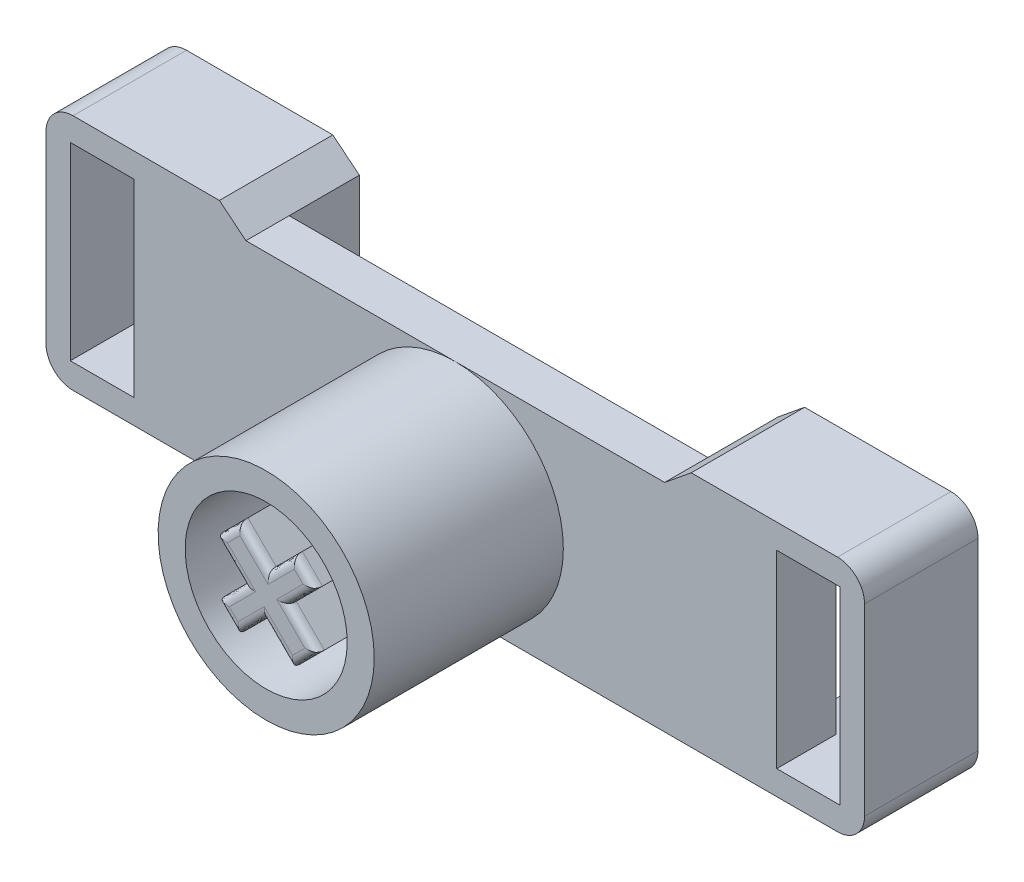
SolidWorks part; units mm, degrees
ref_plane "Front Plane" through (0, 0, 0) normal (0, 0, 1) x (1, 0, 0)
ref_plane "Top Plane" through (0, 0, 0) normal (0, 1, 0) x (1, 0, 0)
ref_plane "Right Plane" through (0, 0, 0) normal (1, 0, 0) x (0, 0, -1)
sketch "Cherry" plane through (0, 0, 0) normal (0, 0, 1) x (1, 0, 0)
  line L0 (-0.8132, -0.0707) -> (-1.8562, 0.9723)
  line L1 (0.9723, -1.8562) -> (-0.0707, -0.8132)
  line L2 (0.9723, -1.8562) -> (1.8562, -0.9723)
  line L3 (1.8562, -0.9723) -> (0.8132, 0.0707)
  line L4 (-1.8562, 0.9723) -> (-0.9723, 1.8562)
  line L6 (0.0707, 0.8132) -> (-0.9723, 1.8562)
  line L7 (-1.043, -1.7854) -> (-1.7854, -1.043)
  line L8 (-1.043, -1.7854) -> (-0.0707, -0.8132)
  line L9 (1.7854, 1.043) -> (1.043, 1.7854)
  line L10 (-1.7854, -1.043) -> (-0.8132, -0.0707)
  line L15 (0.8132, 0.0707) -> (1.7854, 1.043)
  line L18 (0.0707, 0.8132) -> (1.043, 1.7854)
  circle A0 centre (0, 0) radius 3
  circle A1 centre (0, 0) radius 4
extrude "Outer Cylinder" add sketch "Cherry" along normal blind 7 contours L18 L6 L4 L0 L10 L7 L8 L1 L2 L3 L15 L9 | A1 A0 region at (0, 0, 0) region at (-3.8869, 0, 0)
sketch "Inner Gap" plane through (0, 0, 0) normal (0, 0, 1) x (1, 0, 0)
  circle A0 centre (0, 0) radius 3
extrude "Inner Wall" add sketch "Inner Gap" along normal blind 3
fillet "Fillet2" radius 0.3 12 edges at (-1.4142, 1.4142, 7) (-1.3347, 0.4508, 7) (-1.2993, -0.5568, 7) (-1.4142, -1.4142, 7) (-0.5568, -1.2993, 7) (0.4508, -1.3347, 7) (1.4142, -1.4142, 7) (1.3347, -0.4508, 7) (-0.4508, 1.3347, 7) (0.5568, 1.2993, 7) (1.4142, 1.4142, 7) (1.2993, 0.5568, 7) curvature continuous yes
sketch "Sketch2" plane through (0, 0, 0) normal (0, 0, 1) x (1, 0, 0)
  line L0 (-1.8562, 0.9723) -> (-2.8284, 0)
  line L1 (-1.043, -1.7854) -> (-0.0707, -0.8132)
  line L2 (-0.9723, 1.8562) -> (0.0707, 0.8132)
  line L3 (-0.8132, -0.0707) -> (-1.7854, -1.043)
  line L4 (0.9723, -1.8562) -> (0, -2.8284)
  line L5 (0, -1000) -> (0, 49000) construction
  line L6 (-1000, 0) -> (49000, 0) construction
  line L7 (-15.15, -996.1639) -> (-15.15, 49003.8361) construction
  line L8 (-11.7, -997.4571) -> (-11.7, 49002.5429) construction
  line L9 (-14.25, -997.5605) -> (-14.25, 49002.4395) construction
  line L10 (-7.75, -998.1554) -> (-7.75, 49001.8446) construction
  line L11 (-0.9723, 1.8562) -> (0, 2.8284)
  line L12 (-1001.5043, 4) -> (48998.4957, 4) construction
  line L13 (0, 2.8284) -> (1.043, 1.7854)
  line L14 (-1001.5043, -4) -> (48998.4957, -4) construction
  line L15 (0.8132, 0.0707) -> (1.7854, 1.043)
  line L16 (1.7854, 1.043) -> (2.8284, 0)
  line L17 (0.8132, 0.0707) -> (1.8562, -0.9723)
  line L18 (0.0707, 0.8132) -> (1.043, 1.7854)
  line L19 (2.8284, 0) -> (1.8562, -0.9723)
  line L20 (0.9723, -1.8562) -> (-0.0707, -0.8132)
  line L21 (-1004.1116, 4.8) -> (48995.8884, 4.8) construction
  line L22 (-15.15, -3) -> (-15.15, 3.8062)
  line L23 (0, -2.8284) -> (-1.043, -1.7854)
  line L24 (-14.1489, 4.8062) -> (-8.7319, 4.8)
  line L25 (-1.7854, -1.043) -> (-2.8284, 0)
  line L26 (-0.8132, -0.0707) -> (-1.8562, 0.9723)
  line L28 (-7.75, 4) -> (7.75, 4)
  line L29 (-14.15, -4) -> (14.15, -4)
  line L30 (-8.75, -997.4752) -> (-8.75, 49002.5248) construction
  line L31 (-8.7319, 4.8) -> (-7.75, 4)
  line L32 (-1003.474, -3.1) -> (48996.526, -3.1) construction
  line L33 (-1010.3803, 3.9) -> (48989.6197, 3.9) construction
  line L38 (7.75, -998.1554) -> (7.75, 49001.8446) construction
  line L39 (8.75, -997.4752) -> (8.75, 49002.5248) construction
  line L40 (11.7, -997.4571) -> (11.7, 49002.5429) construction
  line L41 (14.25, -997.5605) -> (14.25, 49002.4395) construction
  line L42 (15.15, -996.1639) -> (15.15, 49003.8361) construction
  line L47 (8.7319, 4.8) -> (7.75, 4)
  line L48 (14.1489, 4.8062) -> (8.7319, 4.8)
  line L49 (15.15, -3) -> (15.15, 3.8062)
  arc A0 (15.15, -3) -> (14.15, -4) centre (14.15, -3) cw
  arc A1 (14.1489, 4.8062) -> (15.15, 3.8062) centre (14.15, 3.8062) cw
  arc A2 (-15.15, -3) -> (-14.15, -4) centre (-14.15, -3) ccw
  arc A3 (-15.15, 3.8062) -> (-14.1489, 4.8062) centre (-14.15, 3.8062) cw
  point P41 (0, 4)
  point P69 (0, -4)
  point P71 (15.15, -4)
  point P74 (15.15, 4.8073)
  point P77 (-15.15, -4)
  point P80 (-15.15, 4.8073)
  dimension "D1" = 15.15
  dimension "D10" = 1
  dimension "D2" = 0.9
  dimension "D3" = 2.55
  dimension "D4" = 7.4
  dimension "D5" = 4
  dimension "D6" = 4.8
  dimension "D7" = 1
  dimension "D8" = 0.9
  dimension "D9" = 0.9
extrude "Boss-Extrude1" add sketch "Sketch2" against normal blind 4.2
sketch "Sketch3" plane through (0, 0, 0) normal (0, 0, 1) x (1, 0, 0)
  line L0 (-1.8562, 0.9723) -> (-2.8284, 0)
  line L1 (-1.043, -1.7854) -> (-0.0707, -0.8132)
  line L2 (-0.9723, 1.8562) -> (0.0707, 0.8132)
  line L3 (-0.8132, -0.0707) -> (-1.7854, -1.043)
  line L4 (0.9723, -1.8562) -> (0, -2.8284)
  line L11 (-0.9723, 1.8562) -> (0, 2.8284)
  line L13 (0, 2.8284) -> (1.043, 1.7854)
  line L15 (0.8132, 0.0707) -> (1.7854, 1.043)
  line L16 (1.7854, 1.043) -> (2.8284, 0)
  line L17 (0.8132, 0.0707) -> (1.8562, -0.9723)
  line L18 (0.0707, 0.8132) -> (1.043, 1.7854)
  line L19 (2.8284, 0) -> (1.8562, -0.9723)
  line L20 (0.9723, -1.8562) -> (-0.0707, -0.8132)
  line L23 (0, -2.8284) -> (-1.043, -1.7854)
  line L25 (-1.7854, -1.043) -> (-2.8284, 0)
  line L26 (-0.8132, -0.0707) -> (-1.8562, 0.9723)
extrude "Cut-Extrude1" cut sketch "Sketch3" along normal blind 3 and the other way blind 1.6
sketch "Sketch5" plane through (0, 0, -4.2) normal (0, 0, -1) x (-1, 0, 0)
  line L0 (0, -1000) -> (0, 49000) construction
  line L1 (-7.75, -1000.8733) -> (-7.75, 48999.1267) construction
  line L2 (-1000.8968, 4) -> (48999.1032, 4) construction
  line L3 (-1000, 0) -> (49000, 0) construction
  line L4 (-1000.8968, -4) -> (48999.1032, -4) construction
  line L5 (7.75, -1000.8733) -> (7.75, 48999.1267) construction
  line L7 (-7.75, 4) -> (7.75, 4)
  line L8 (-7.75, 4) -> (-7.75, -4)
  line L9 (-7.75, -4) -> (7.75, -4)
  line L10 (7.75, 4) -> (7.75, -4)
  dimension "D1" = 4
  dimension "D2" = 7.75
extrude "Cut-Extrude2" cut sketch "Sketch5" against normal blind 2.6
sketch "Sketch6" plane through (0, 0, 0) normal (0, 0, 1) x (1, 0, 0)
  line L0 (1010.3803, 3.9) -> (-48989.6197, 3.9) construction
  line L1 (-14.25, 3.9) -> (-11.9, 3.9)
  line L2 (-14.25, 3.9) -> (-14.25, -3.1)
  line L3 (-14.25, -3.1) -> (-11.9, -3.1)
  line L4 (-11.9, 3.9) -> (-11.9, -3.1)
  line L5 (0, -1000) -> (0, 49000) construction
  line L6 (-1000, 0) -> (49000, 0) construction
  line L7 (-15.15, -996.1639) -> (-15.15, 49003.8361) construction
  line L8 (-11.9, -997.4571) -> (-11.9, 49002.5429) construction
  line L9 (-14.25, -997.5605) -> (-14.25, 49002.4395) construction
  line L10 (-7.75, -998.1554) -> (-7.75, 49001.8446) construction
  line L11 (1003.474, -3.1) -> (-48996.526, -3.1) construction
  line L12 (-1001.5043, 4) -> (48998.4957, 4) construction
  line L13 (1001.5043, 4) -> (-48998.4957, 4) construction
  line L14 (-1001.5043, -4) -> (48998.4957, -4) construction
  line L16 (11.9, -997.4571) -> (11.9, 49002.5429) construction
  line L17 (1000, 0) -> (-49000, 0) construction
  line L18 (11.9, 3.9) -> (11.9, -3.1)
  line L19 (14.25, -3.1) -> (11.9, -3.1)
  line L20 (14.25, 3.9) -> (14.25, -3.1)
  line L21 (-1004.1116, 4.8) -> (48995.8884, 4.8) construction
  line L22 (14.25, 3.9) -> (11.9, 3.9)
  line L30 (-8.75, -997.4752) -> (-8.75, 49002.5248) construction
  line L32 (-1003.474, -3.1) -> (48996.526, -3.1) construction
  line L33 (-1010.3803, 3.9) -> (48989.6197, 3.9) construction
  line L38 (7.75, -998.1554) -> (7.75, 49001.8446) construction
  line L39 (8.75, -997.4752) -> (8.75, 49002.5248) construction
  line L41 (14.25, -997.5605) -> (14.25, 49002.4395) construction
  line L42 (15.15, -996.1639) -> (15.15, 49003.8361) construction
  point P41 (0, 4)
  point P69 (0, -4)
  point P71 (15.15, -4)
  point P74 (15.15, 4.8073)
  point P77 (-15.15, -4)
  point P80 (-15.15, 4.8073)
  dimension "D1" = 15.15
  dimension "D2" = 0.9
  dimension "D3" = 2.35
  dimension "D4" = 7.4
  dimension "D5" = 4
  dimension "D6" = 4.8
  dimension "D7" = 1
  dimension "D8" = 0.9
  dimension "D9" = 0.9
extrude "Cut-Extrude3" cut sketch "Sketch6" against normal blind 3.3
sketch "Sketch8" plane through (0, 0, -4.2) normal (0, 0, 1) x (1, 0, 0)
  line L0 (-1010.2744, 1.9) -> (48989.7256, 1.9) construction
  line L1 (-10.75, -1001.0626) -> (-10.75, 48998.9374) construction
  line L3 (-10.75, -4) -> (-10.75, -3.1)
  line L4 (-10.75, -3.1) -> (-12.25, -3.1)
  line L5 (0, -1000) -> (0, 49000) construction
  line L6 (-1000, 0) -> (49000, 0) construction
  line L7 (-15.15, -996.1639) -> (-15.15, 49003.8361) construction
  line L8 (-12.25, -997.4571) -> (-12.25, 49002.5429) construction
  line L9 (-14.25, -997.5605) -> (-14.25, 49002.4395) construction
  line L10 (-7.75, -998.1554) -> (-7.75, 49001.8446) construction
  line L11 (-12.25, -3.1) -> (-12.25, 1.9)
  line L12 (-12.25, 1.9) -> (-14.25, 1.9)
  line L13 (-10.75, -4) -> (-8.6534, -4)
  line L14 (-1001.5043, -4) -> (48998.4957, -4) construction
  line L15 (-14.25, 3.9) -> (-14.25, 1.9)
  line L16 (-14.25, 3.9) -> (-8.65, 3.9)
  line L18 (-8.65, 3.9) -> (-8.6534, -4)
  line L19 (8.65, 3.9) -> (8.6534, -4)
  line L21 (-1004.1116, 4.8) -> (48995.8884, 4.8) construction
  line L22 (14.25, 3.9) -> (8.65, 3.9)
  line L23 (14.25, 3.9) -> (14.25, 1.9)
  line L24 (10.75, -4) -> (8.6534, -4)
  line L25 (12.25, 1.9) -> (14.25, 1.9)
  line L27 (12.25, -3.1) -> (12.25, 1.9)
  line L28 (10.75, -3.1) -> (12.25, -3.1)
  line L29 (10.75, -4) -> (10.75, -3.1)
  line L30 (-8.65, -997.4752) -> (-8.65, 49002.5248) construction
  line L32 (-1003.474, -3.1) -> (48996.526, -3.1) construction
  line L33 (-1010.3803, 3.9) -> (48989.6197, 3.9) construction
  line L38 (7.75, -998.1554) -> (7.75, 49001.8446) construction
  line L39 (8.65, -997.4752) -> (8.65, 49002.5248) construction
  line L40 (12.25, -997.4571) -> (12.25, 49002.5429) construction
  line L41 (14.25, -997.5605) -> (14.25, 49002.4395) construction
  line L42 (15.15, -996.1639) -> (15.15, 49003.8361) construction
  point P69 (0, -4)
  point P71 (15.15, -4)
  point P74 (15.15, 4.8073)
  point P77 (-15.15, -4)
  point P80 (-15.15, 4.8073)
  dimension "D1" = 15.15
  dimension "D10" = 4.4
  dimension "D2" = 0.9
  dimension "D3" = 2.9
  dimension "D4" = 7.4
  dimension "D5" = 5.9
  dimension "D6" = 4.8
  dimension "D7" = 0.9
  dimension "D8" = 0.9
  dimension "D9" = 0.9
extrude "Cut-Extrude4" cut sketch "Sketch8" along normal blind 2
sketch "Sketch10" plane through (0, 0, -2.2) normal (0, 0, -1) x (-1, 0, 0)
  line L0 (-1010.2744, 1.9) -> (48989.7256, 1.9) construction
  line L1 (-11, -1001.0626) -> (-11, 48998.9374) construction
  line L2 (-10.75, -1002.0108) -> (-10.75, 48997.9892) construction
  line L3 (-10.75, -4) -> (-10.75, -3.1)
  line L4 (-10.75, -3.1) -> (-11, -3.1)
  line L5 (0, -1000) -> (0, 49000) construction
  line L6 (-1000, 0) -> (49000, 0) construction
  line L7 (-15.15, -996.1639) -> (-15.15, 49003.8361) construction
  line L8 (-11.9, -997.4571) -> (-11.9, 49002.5429) construction
  line L9 (-14.25, -997.5605) -> (-14.25, 49002.4395) construction
  line L10 (-7.75, -998.1554) -> (-7.75, 49001.8446) construction
  line L11 (-11, -3.1) -> (-11, 3.9)
  line L12 (-11, 3.9) -> (-8.65, 3.9)
  line L13 (-8.65, 3.9) -> (-8.6534, -4)
  line L14 (-1001.5043, -4) -> (48998.4957, -4) construction
  line L15 (-8.6534, -4) -> (-10.75, -4)
  line L16 (8.6534, -4) -> (10.75, -4)
  line L17 (8.65, 3.9) -> (8.6534, -4)
  line L18 (11, 3.9) -> (8.65, 3.9)
  line L19 (11, -3.1) -> (11, 3.9)
  line L20 (10.75, -3.1) -> (11, -3.1)
  line L21 (-1004.1116, 4.8) -> (48995.8884, 4.8) construction
  line L22 (10.75, -4) -> (10.75, -3.1)
  line L30 (-8.65, -997.4752) -> (-8.65, 49002.5248) construction
  line L32 (-1003.474, -3.1) -> (48996.526, -3.1) construction
  line L33 (-1010.3803, 3.9) -> (48989.6197, 3.9) construction
  line L38 (7.75, -998.1554) -> (7.75, 49001.8446) construction
  line L39 (8.65, -997.4752) -> (8.65, 49002.5248) construction
  line L40 (11.9, -997.4571) -> (11.9, 49002.5429) construction
  line L41 (14.25, -997.5605) -> (14.25, 49002.4395) construction
  line L42 (15.15, -996.1639) -> (15.15, 49003.8361) construction
  point P69 (0, -4)
  point P71 (15.15, -4)
  point P74 (15.15, 4.8073)
  point P77 (-15.15, -4)
  point P80 (-15.15, 4.8073)
  dimension "D1" = 15.15
  dimension "D10" = 0.9
  dimension "D2" = 0.9
  dimension "D3" = 2.35
  dimension "D4" = 7.4
  dimension "D5" = 5.9
  dimension "D6" = 4.8
  dimension "D7" = 0.9
  dimension "D8" = 0.9
  dimension "D9" = 0.9
  dimension "D11" = 4.4
extrude "Cut-Extrude5" cut sketch "Sketch10" against normal blind 0.4
